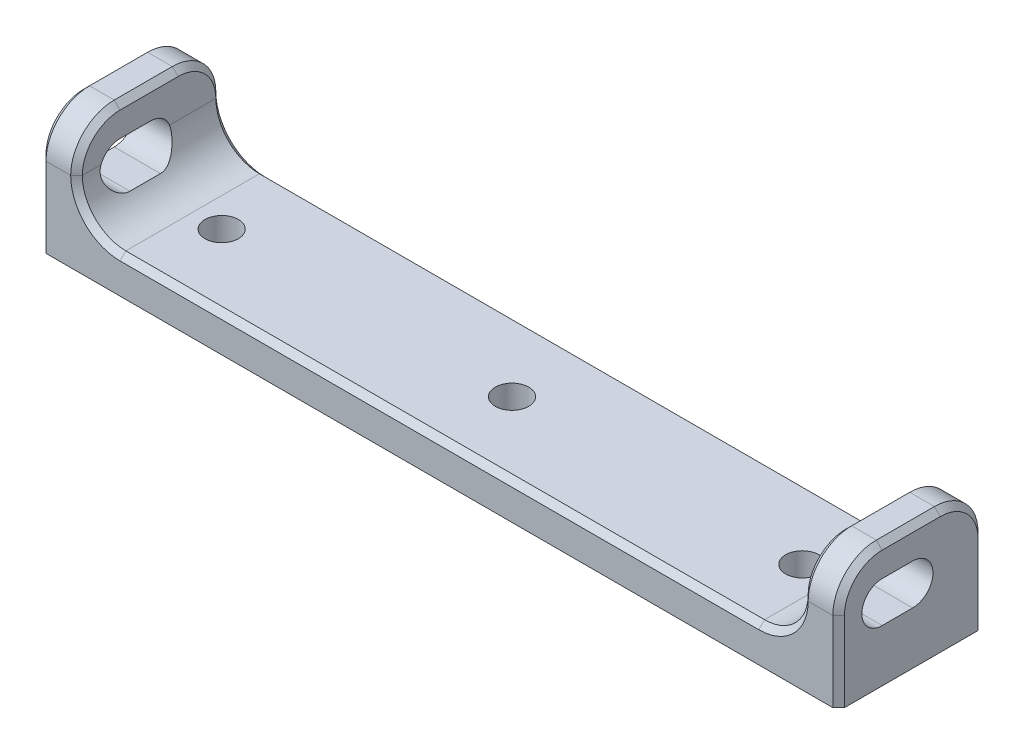
SolidWorks part; units mm, degrees
ref_plane "Front Plane" through (0, 0, 0) normal (0, 0, 1) x (1, 0, 0)
ref_plane "Top Plane" through (0, 0, 0) normal (0, 1, 0) x (1, 0, 0)
ref_plane "Right Plane" through (0, 0, 0) normal (1, 0, 0) x (0, 0, -1)
sketch "Sketch1" plane through (0, 0, 0) normal (0, 0, 1) x (1, 0, 0)
  line L0 (0, 0) -> (0, 21.59)
  line L1 (0, 21.59) -> (6.35, 21.59)
  line L2 (6.35, 21.59) -> (6.35, 6.35)
  line L3 (6.35, 6.35) -> (133.35, 6.35)
  line L4 (133.35, 6.35) -> (133.35, 21.59)
  line L5 (133.35, 21.59) -> (139.7, 21.59)
  line L6 (139.7, 21.59) -> (139.7, 0)
  line L7 (139.7, 0) -> (0, 0)
  dimension "D1" = 6.35
  dimension "D2" = 15.24
  dimension "D3" = 6.35
  dimension "D4" = 127
extrude "Boss-Extrude1" add sketch "Sketch1" along normal blind 25.4
fillet "Fillet1" radius 7.62 6 edges at (136.525, 21.59, 0) (136.525, 21.59, 25.4) (3.175, 21.59, 0) (3.175, 21.59, 25.4) (133.35, 6.35, 12.7) (6.35, 6.35, 12.7)
sketch "Sketch2" plane through (0, 6.35, 0) normal (0, 1, 0) x (1, 0, 0)
  line L0 (69.85, 0) -> (69.85, -25.4) construction
  line L1 (125.73, -25.4) -> (13.97, -25.4) construction
  line L2 (125.73, 0) -> (13.97, 0) construction
  circle A0 centre (69.85, -12.7) radius 2.921
  circle A1 centre (120.65, -12.7) radius 2.921
  circle A2 centre (19.05, -12.7) radius 2.921
  dimension "D1" = 5.842
  dimension "D2" = 50.8
  dimension "D3" = 50.8
extrude "Cut-Extrude1" cut sketch "Sketch2" against normal through all
chamfer "Chamfer1" distance 1.016 angle 45 22 edges at (0, 6.985, 25.4) (0, 19.3582, 23.1682) (0, 21.59, 12.7) (0, 19.3582, 2.2318) (0, 6.985, 0) (139.7, 6.985, 25.4) (139.7, 6.985, 0) (139.7, 19.3582, 2.2318) (139.7, 21.59, 12.7) (139.7, 19.3582, 23.1682) (133.35, 19.3582, 23.1682) (133.35, 21.59, 12.7) (133.35, 19.3582, 2.2318) (131.1182, 8.5818, 0) (69.85, 6.35, 0) (8.5818, 8.5818, 0) (6.35, 19.3582, 2.2318) (6.35, 21.59, 12.7) (6.35, 19.3582, 23.1682) (8.5818, 8.5818, 25.4) (69.85, 6.35, 25.4) (131.1182, 8.5818, 25.4)
sketch "Sketch3" plane through (139.7, 0, 0) normal (1, 0, 0) x (0, 0, -1)
  line L0 (-12.7, 0) -> (-12.7, 20.574) construction
  line L1 (-24.384, 0) -> (-1.016, 0) construction
  line L2 (-7.62, 20.574) -> (-17.78, 20.574) construction
  line L3 (-30.1584, 12.7) -> (1.5364, 12.7) construction
  line L4 (-17.78, 16.256) -> (-12.446, 16.256)
  line L5 (-17.78, 9.144) -> (-12.446, 9.144)
  arc A1 (-12.446, 16.256) -> (-12.446, 9.144) centre (-12.446, 12.7) cw
  arc A2 (-17.78, 16.256) -> (-17.78, 9.144) centre (-17.78, 12.7) ccw
  dimension "D1" = 12.7
  dimension "D4" = 3.556
  dimension "D2" = 0.254
  dimension "D3" = 5.08
extrude "Cut-Extrude2" cut sketch "Sketch3" against normal through all
